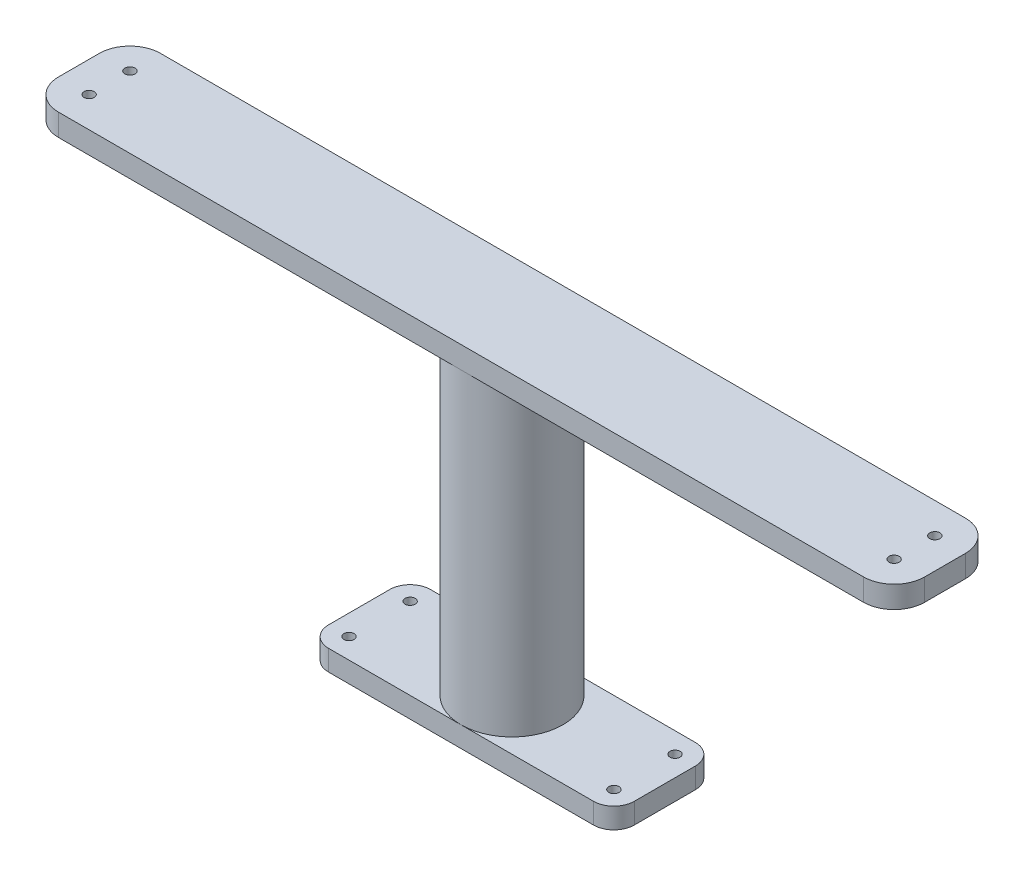
SolidWorks part; units mm, degrees
ref_plane "Front Plane" through (0, 0, 0) normal (0, 0, 1) x (1, 0, 0)
ref_plane "Top Plane" through (0, 0, 0) normal (0, 1, 0) x (1, 0, 0)
ref_plane "Right Plane" through (0, 0, 0) normal (1, 0, 0) x (0, 0, -1)
sketch "Sketch1" plane through (0, 0, 0) normal (0, 1, 0) x (1, 0, 0)
  line L1 (-395, 50) -> (395, 50)
  line L2 (-425, 20) -> (-425, -20)
  line L3 (-395, -50) -> (395, -50)
  line L4 (425, 20) -> (425, -20)
  line L5 (-425, 50) -> (425, -50) construction
  line L6 (-425, -50) -> (425, 50) construction
  arc A0 (-395, 50) -> (-425, 20) centre (-395, 20) ccw
  arc A1 (-425, -20) -> (-395, -50) centre (-395, -20) ccw
  arc A2 (395, -50) -> (425, -20) centre (395, -20) ccw
  arc A3 (395, 50) -> (425, 20) centre (395, 20) cw
  circle A4 centre (-395, 20) radius 5
  circle A5 centre (-395, -20) radius 5
  circle A6 centre (395, 20) radius 5
  circle A7 centre (395, -20) radius 5
  point P0 (0, 0)
  dimension "D3" = 30
  dimension "D4" = 10
  dimension "D5" = 10
  dimension "D6" = 10
  dimension "D7" = 10
  dimension "D1" = 100
  dimension "D2" = 850
extrude "Boss-Extrude1" add sketch "Sketch1" along normal blind 1.5875
sketch "Sketch2" plane through (0, 0, 0) normal (0, -1, 0) x (1, 0, 0)
  line L0 (-395, 50) -> (395, 50) construction
  circle A0 centre (0, 0) radius 50
  circle A1 centre (0, 0) radius 45
  dimension "D1" = 5
extrude "Boss-Extrude2" add sketch "Sketch2" along normal blind 341.625
sketch "Sketch3" plane through (0, -341.625, 0) normal (0, -1, 0) x (1, 0, 0)
  line L0 (395, -50) -> (0, -50) construction
  line L1 (-130, 50) -> (130, 50)
  line L2 (-150, 30) -> (-150, -30)
  line L3 (-130, -50) -> (130, -50)
  line L4 (150, 30) -> (150, -30)
  line L5 (-150, 50) -> (150, -50) construction
  line L6 (-150, -50) -> (150, 50) construction
  arc A0 (-130, 50) -> (-150, 30) centre (-130, 30) ccw
  arc A1 (-150, -30) -> (-130, -50) centre (-130, -30) ccw
  arc A2 (130, -50) -> (150, -30) centre (130, -30) ccw
  arc A3 (130, 50) -> (150, 30) centre (130, 30) cw
  circle A4 centre (-130, 30) radius 5
  circle A5 centre (-130, -30) radius 5
  circle A6 centre (130, 30) radius 5
  circle A7 centre (130, -30) radius 5
  point P0 (0, 0)
  dimension "D2" = 20
  dimension "D3" = 10
  dimension "D1" = 300
extrude "Boss-Extrude3" add sketch "Sketch3" along normal blind 0.219
sketch "Sketch4" plane through (0, 0, 0) normal (0, -1, 0) x (1, 0, 0)
  line L0 (0, -50) -> (395, -50) construction
  line L1 (425, -20) -> (425, 20) construction
  line L2 (395, 50) -> (0, 50) construction
  line L3 (0, 50) -> (-395, 50) construction
  line L4 (-425, 20) -> (-425, -20) construction
  line L5 (-395, -50) -> (0, -50) construction
  line L6 (0, -50) -> (395, -50)
  line L7 (425, -20) -> (425, 20)
  line L8 (395, 50) -> (0, 50)
  line L9 (0, 50) -> (-395, 50)
  line L10 (-425, 20) -> (-425, -20)
  line L11 (-395, -50) -> (0, -50)
  line L15 (0, -50) -> (395, -50)
  line L16 (425, -20) -> (425, 20)
  line L17 (395, 50) -> (0, 50)
  line L18 (0, -50) -> (395, -50)
  line L19 (425, -20) -> (425, 20)
  line L20 (395, 50) -> (0, 50)
  arc A0 (0, -50) -> (0, 50) centre (0, 0) ccw construction
  arc A1 (395, -50) -> (425, -20) centre (395, -20) ccw construction
  arc A2 (425, 20) -> (395, 50) centre (395, 20) ccw construction
  arc A3 (0, 50) -> (0, -50) centre (0, 0) ccw construction
  arc A4 (-395, 50) -> (-425, 20) centre (-395, 20) ccw construction
  arc A5 (-425, -20) -> (-395, -50) centre (-395, -20) ccw construction
  arc A6 (0, -50) -> (0, 50) centre (0, 0) ccw
  arc A7 (395, -50) -> (425, -20) centre (395, -20) ccw
  arc A8 (425, 20) -> (395, 50) centre (395, 20) ccw
  arc A9 (0, 50) -> (0, -50) centre (0, 0) ccw
  arc A10 (-395, 50) -> (-425, 20) centre (-395, 20) ccw
  arc A11 (-425, -20) -> (-395, -50) centre (-395, -20) ccw
  circle A12 centre (395, 20) radius 5 construction
  circle A13 centre (395, -20) radius 5 construction
  circle A14 centre (395, 20) radius 5
  arc A15 (0, -50) -> (0, 50) centre (0, 0) ccw
  arc A16 (395, -50) -> (425, -20) centre (395, -20) ccw
  arc A17 (425, 20) -> (395, 50) centre (395, 20) ccw
  arc A18 (0, -50) -> (0, 50) centre (0, 0) ccw
  arc A19 (395, -50) -> (425, -20) centre (395, -20) ccw
  arc A20 (425, 20) -> (395, 50) centre (395, 20) ccw
  circle A21 centre (395, -20) radius 5
  arc M1 (0, -50) -> (0, 50) centre (0, 0) cw
  line M2 (0, 50) -> (-395, 50)
  arc M3 (-395, 50) -> (-425, 20) centre (-395, 20) ccw
  line M4 (-425, 20) -> (-425, -20)
  arc M5 (-425, -20) -> (-395, -50) centre (-395, -20) ccw
  line M6 (-395, -50) -> (0, -50)
  circle M7 centre (-395, 20) radius 5
  circle M8 centre (-395, -20) radius 5
  dimension "D1" = 0
extrude "Boss-Extrude4" add sketch "Sketch4" along normal blind 20 contours M6 M1 M2 M3 M4 M5 M7 M8 | L7 A8 L8 A6 L6 A7 region at (229.4076, 0, 0) region at (-229.4076, 0, 0)
sketch "Sketch5" plane through (0, -341.625, 0) normal (0, 1, 0) x (1, 0, 0)
  line L0 (130, 50) -> (0, 50) construction
  line L1 (0, -50) -> (130, -50) construction
  line L2 (150, -30) -> (150, 30) construction
  line L3 (-130, -50) -> (0, -50) construction
  line L4 (0, 50) -> (-130, 50) construction
  line L5 (-150, 30) -> (-150, -30) construction
  line L6 (130, 50) -> (0, 50)
  line L7 (0, -50) -> (130, -50)
  line L8 (150, -30) -> (150, 30)
  line L9 (-130, -50) -> (0, -50)
  line L10 (0, 50) -> (-130, 50)
  line L11 (-150, 30) -> (-150, -30)
  arc A0 (0, -50) -> (0, 50) centre (0, 0) ccw construction
  arc A1 (130, -50) -> (150, -30) centre (130, -30) ccw construction
  arc A2 (150, 30) -> (130, 50) centre (130, 30) ccw construction
  arc A3 (0, 50) -> (0, -50) centre (0, 0) ccw construction
  arc A4 (-130, 50) -> (-150, 30) centre (-130, 30) ccw construction
  arc A5 (-150, -30) -> (-130, -50) centre (-130, -30) ccw construction
  arc A6 (0, -50) -> (0, 50) centre (0, 0) ccw
  arc A7 (130, -50) -> (150, -30) centre (130, -30) ccw
  arc A8 (150, 30) -> (130, 50) centre (130, 30) ccw
  arc A9 (0, 50) -> (0, -50) centre (0, 0) ccw
  arc A10 (-130, 50) -> (-150, 30) centre (-130, 30) ccw
  arc A11 (-150, -30) -> (-130, -50) centre (-130, -30) ccw
  circle A12 centre (-130, -30) radius 5 construction
  circle A13 centre (-130, 30) radius 5 construction
  circle A14 centre (130, -30) radius 5 construction
  circle A15 centre (130, 30) radius 5 construction
  circle A16 centre (-130, -30) radius 5
  circle A17 centre (-130, 30) radius 5
  circle A18 centre (130, -30) radius 5
  circle A19 centre (130, 30) radius 5
  circle M1 centre (-130, 30) radius 5
  circle M2 centre (-130, -30) radius 5
  line M3 (-130, -50) -> (0, -50)
  arc M4 (0, -50) -> (0, 50) centre (0, 0) cw
  line M5 (0, 50) -> (-130, 50)
  arc M6 (-130, 50) -> (-150, 30) centre (-130, 30) ccw
  line M7 (-150, 30) -> (-150, -30)
  arc M8 (-150, -30) -> (-130, -50) centre (-130, -30) ccw
extrude "Boss-Extrude5" add sketch "Sketch5" along normal blind 20 contours M8 M3 M4 M5 M6 M7 M2 M1 | L8 A8 L6 A6 L7 A7 region at (92.7251, -341.625, 0) region at (-92.7251, -341.625, 0)
